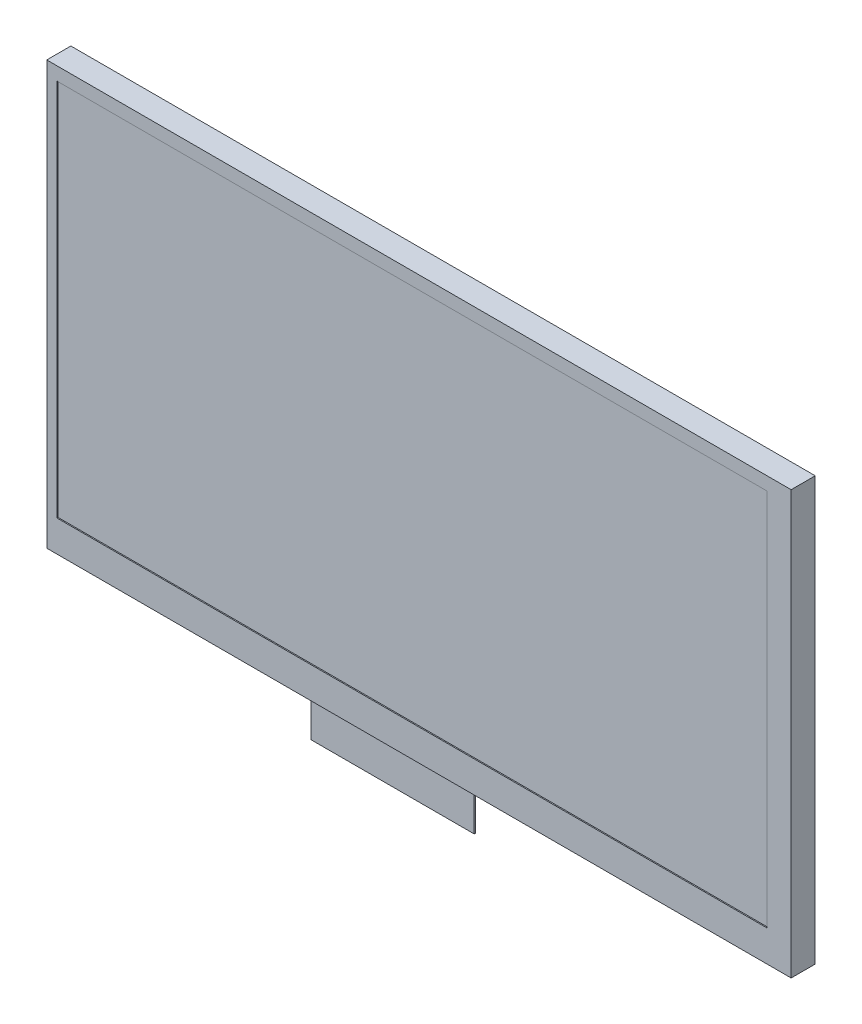
SolidWorks part; units mm, degrees
ref_plane "Front Plane" through (0, 0, 0) normal (0, 0, 1) x (1, 0, 0)
ref_plane "Top Plane" through (0, 0, 0) normal (0, 1, 0) x (1, 0, 0)
ref_plane "Right Plane" through (0, 0, 0) normal (1, 0, 0) x (0, 0, -1)
sketch "Sketch1" plane through (0, 0, 0) normal (0, 0, 1) x (1, 0, 0)
  line L1 (-88.011, -50) -> (88.011, -50)
  line L2 (-88.011, -50) -> (-88.011, 50)
  line L3 (-88.011, 50) -> (88.011, 50)
  line L4 (88.011, -50) -> (88.011, 50)
  line L5 (-88.011, -50) -> (88.011, 50) construction
  line L6 (-88.011, 50) -> (88.011, -50) construction
  line L7 (-85.6234, 46.8758) -> (82.3468, 46.8758)
  line L8 (-85.6234, 46.8758) -> (-85.6234, -42.6086)
  line L9 (-85.6234, -42.6086) -> (82.3468, -42.6086)
  line L10 (82.3468, 46.8758) -> (82.3468, -42.6086)
  point P0 (0, 0)
  dimension "D1" = 5.6642
  dimension "D2" = 100
  dimension "D3" = 167.9702
  dimension "D4" = 7.3914
  dimension "D5" = 3.1242
  dimension "D6" = 2.3876
extrude "Boss-Extrude1" add sketch "Sketch1" against normal blind 5.7 contours L10 L7 L8 L9 | L1 L4 L3 L2 L7 L10 L9 L8 region at (-85.9866, 0, 0) region at (-1.6383, 2.1336, 0)
extrude "Cut-Extrude1" cut sketch "Sketch1<3>" against normal blind 0.254 contours L10 L7 L8 L9 region at (-1.6383, 2.1336, 0)
sketch "Sketch1<3>" plane through (0, 0, 0) normal (0, 0, 1) x (1, 0, 0) same geometry as "Sketch1"
sketch "Sketch2" plane through (0, 0, 0) normal (0, 0, 1) x (1, 0, 0)
  line L0 (-88.011, -50) -> (88.011, -50) construction
  line L1 (-26.6446, -50) -> (11.8948, -50)
  line L2 (-26.6446, -50) -> (-26.6446, -59.144)
  line L3 (-26.6446, -59.144) -> (11.8948, -59.144)
  line L4 (11.8948, -50) -> (11.8948, -59.144)
  line L6 (-88.011, -50) -> (-88.011, 50) construction
  dimension "D1" = 61.3664
  dimension "D2" = 38.5394
  dimension "D3" = 9.144
extrude "Boss-Extrude2" add sketch "Sketch2" against normal blind 0.3048 from offset 1.1684 offset against normal yes
